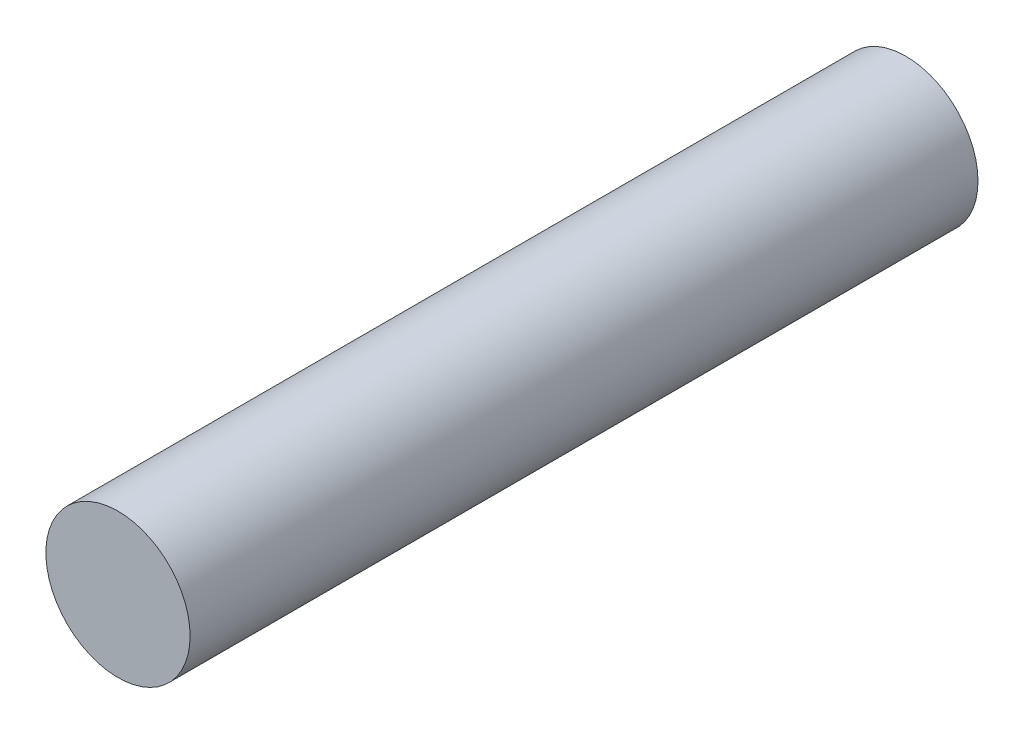
SolidWorks part; units mm, degrees
ref_plane "Front Plane" through (0, 0, 0) normal (0, 0, 1) x (1, 0, 0)
ref_plane "Top Plane" through (0, 0, 0) normal (0, 1, 0) x (1, 0, 0)
ref_plane "Right Plane" through (0, 0, 0) normal (1, 0, 0) x (0, 0, -1)
sketch "Sketch3" plane through (0, 0, 0) normal (0, 0, 1) x (1, 0, 0)
  circle A0 centre (0, 0) radius 78.35
  dimension "D1" = 156.7
extrude "Boss-Extrude1" add sketch "Sketch3" against normal blind 855.898
